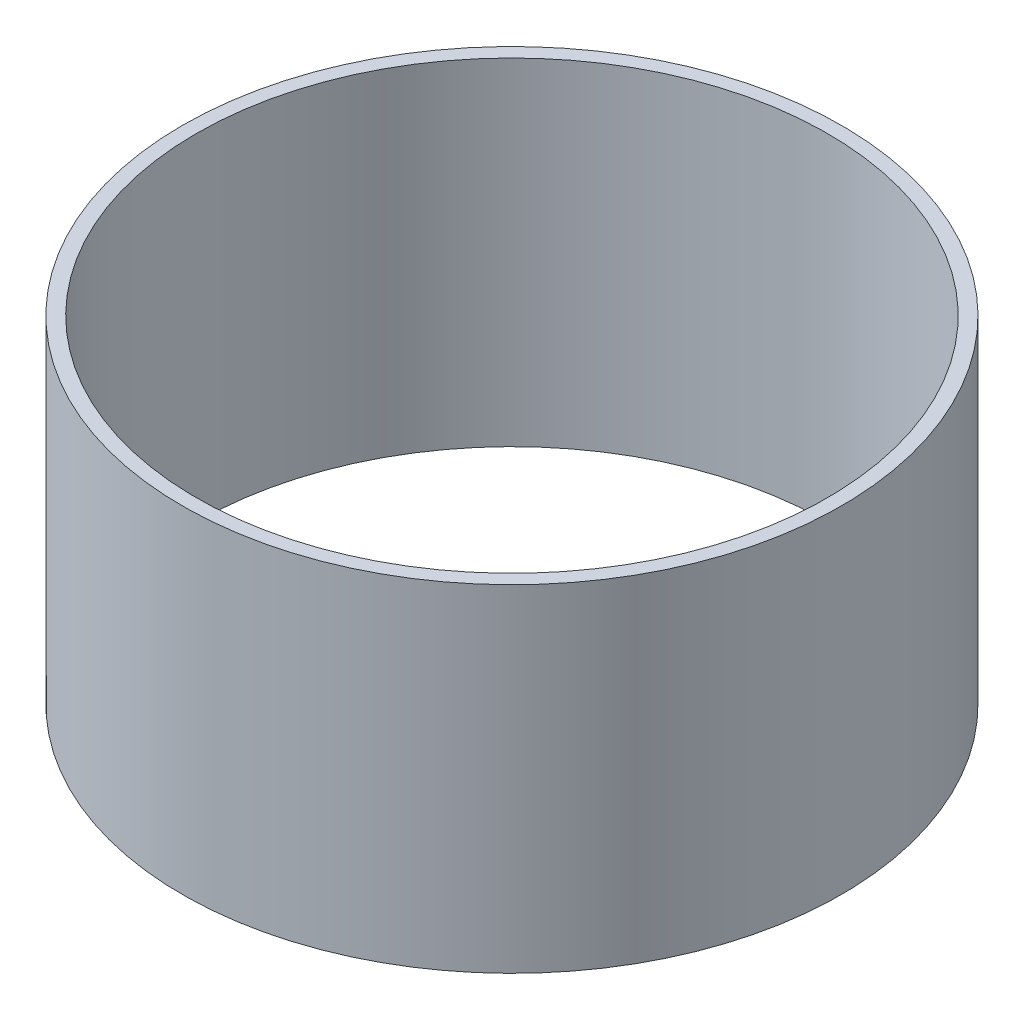
SolidWorks part; units mm, degrees
ref_plane "Front Plane" through (0, 0, 0) normal (0, 0, 1) x (1, 0, 0)
ref_plane "Top Plane" through (0, 0, 0) normal (0, 1, 0) x (1, 0, 0)
ref_plane "Right Plane" through (0, 0, 0) normal (1, 0, 0) x (0, 0, -1)
sketch "Sketch1" plane through (0, -229.1873, 0) normal (0, 1, 0) x (1, 0, 0)
  circle A0 centre (0, 0) radius 285.75
  circle A1 centre (0, 0) radius 298.45
  dimension "D1" = 571.5
  dimension "D2" = 596.9
extrude "Boss-Extrude1" add sketch "Sketch1" against normal blind 304.8
